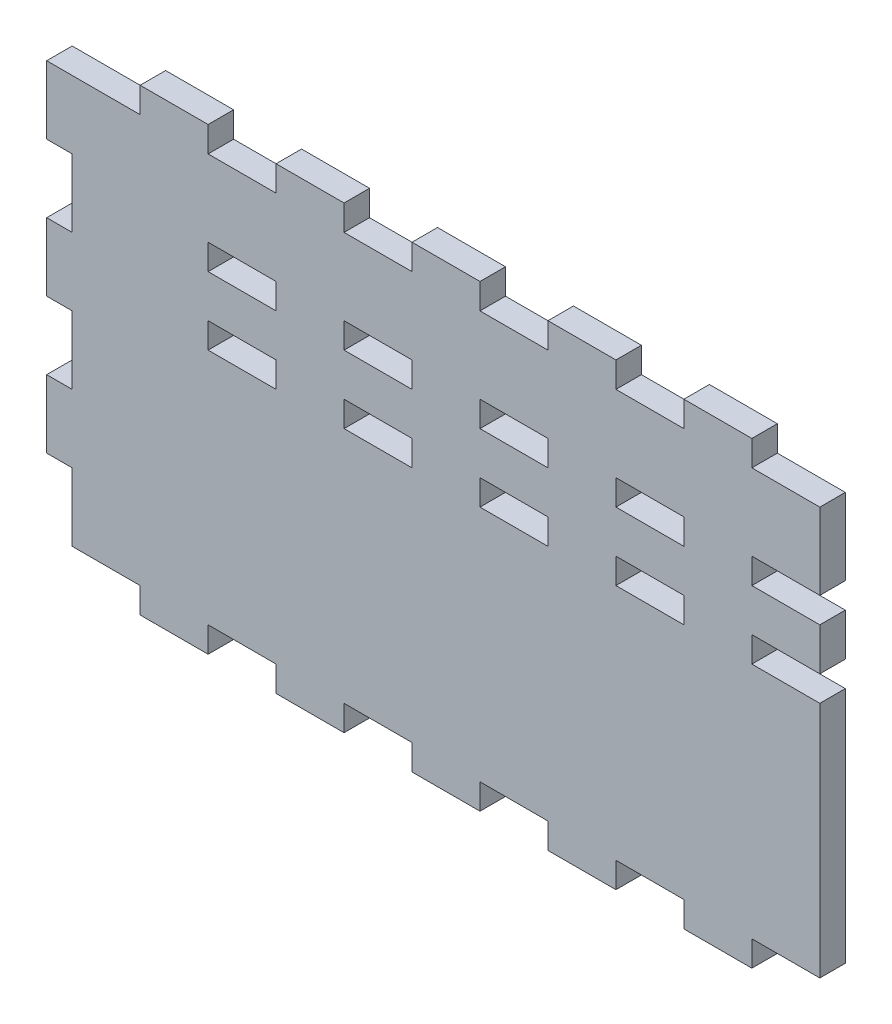
SolidWorks part; units mm, degrees
ref_plane "Front Plane" through (0, 0, 0) normal (0, 0, 1) x (1, 0, 0)
ref_plane "Top Plane" through (0, 0, 0) normal (0, 1, 0) x (1, 0, 0)
ref_plane "Right Plane" through (0, 0, 0) normal (1, 0, 0) x (0, 0, -1)
sketch "Sketch1" plane through (0, 0, 0) normal (0, 0, 1) x (1, 0, 0)
  line L1 (-139.7, -76.2) -> (139.7, -76.2)
  line L2 (-139.7, -76.2) -> (-139.7, 76.2)
  line L3 (-139.7, 76.2) -> (139.7, 76.2)
  line L4 (139.7, -76.2) -> (139.7, 76.2)
  line L5 (-139.7, -76.2) -> (139.7, 76.2) construction
  line L6 (-139.7, 76.2) -> (139.7, -76.2) construction
  point P0 (0, 0)
  dimension "D1" = 279.4
  dimension "D2" = 152.4
extrude "Boss-Extrude1" add sketch "Sketch1" along normal blind 9.525
sketch "Sketch2" plane through (0, -76.2, 0) normal (0, -1, 0) x (1, 0, 0)
  line L0 (-139.7, 0) -> (139.7, 0) construction
  line L1 (-114.3, 0) -> (-88.9, 0)
  line L2 (-114.3, 0) -> (-114.3, 9.525)
  line L3 (-114.3, 9.525) -> (-88.9, 9.525)
  line L4 (-88.9, 0) -> (-88.9, 9.525)
  line L5 (-139.7, 9.525) -> (139.7, 9.525) construction
  line L6 (-139.7, 9.525) -> (-139.7, 0) construction
  point P10 (-139.7, 4.7625)
  dimension "D1" = 25.4
  dimension "D2" = 25.4
extrude "Boss-Extrude2" add sketch "Sketch2" along normal blind 9.525
pattern_linear "LPattern1" count 5 spacing 50.8 along (1, 0, 0) of "Boss-Extrude2"
mirror "Mirror1" about plane through (0, 0, 0) normal (0, 1, 0) of "LPattern1"
sketch "Sketch3" plane through (-139.7, 0, 0) normal (-1, 0, 0) x (0, 0, 1)
  line L0 (0, 76.2) -> (0, -76.2) construction
  line L1 (9.525, 76.2) -> (0, 76.2)
  line L2 (9.525, 76.2) -> (9.525, 50.8)
  line L3 (9.525, 50.8) -> (0, 50.8)
  line L4 (0, 76.2) -> (0, 50.8)
  dimension "D1" = 25.4
extrude "Boss-Extrude3" add sketch "Sketch3" along normal blind 9.525
pattern_linear "LPattern2" count 3 spacing 50.8 along (0, -1, 0) of "Boss-Extrude3"
sketch "Sketch4" plane through (0, 0, 0) normal (0, 0, -1) x (-1, 0, 0)
  line L1 (-139.7, 12.7) -> (-114.3, 12.7)
  line L2 (-139.7, 12.7) -> (-139.7, 22.225)
  line L3 (-139.7, 22.225) -> (-114.3, 22.225)
  line L4 (-114.3, 12.7) -> (-114.3, 22.225)
  line L5 (-114.3, -76.2) -> (-139.7, -76.2) construction
  line L6 (-139.7, -76.2) -> (-139.7, 76.2) construction
  dimension "D1" = 25.4
  dimension "D2" = 9.525
  dimension "D4" = 88.9
extrude "Cut-Extrude1" cut sketch "Sketch4" against normal through all
pattern_linear "LPattern3" count 5 spacing 50.8 along (-1, 0, 0) of "Cut-Extrude1"
sketch "Sketch5" plane through (0, 0, 9.525) normal (0, 0, 1) x (1, 0, 0)
  line L0 (-88.9, 12.7) -> (-88.9, 22.225) construction
  line L1 (-63.5, 47.625) -> (-88.9, 47.625)
  line L2 (-63.5, 47.625) -> (-63.5, 38.1)
  line L3 (-63.5, 38.1) -> (-88.9, 38.1)
  line L4 (-88.9, 47.625) -> (-88.9, 38.1)
  line L5 (-88.9, -76.2) -> (-63.5, -76.2) construction
  dimension "D1" = 25.4
  dimension "D2" = 9.525
  dimension "D3" = 114.3
extrude "Cut-Extrude2" cut sketch "Sketch5" against normal through all
pattern_linear "LPattern4" count 5 spacing 50.8 along (1, 0, 0) of "Cut-Extrude2"
